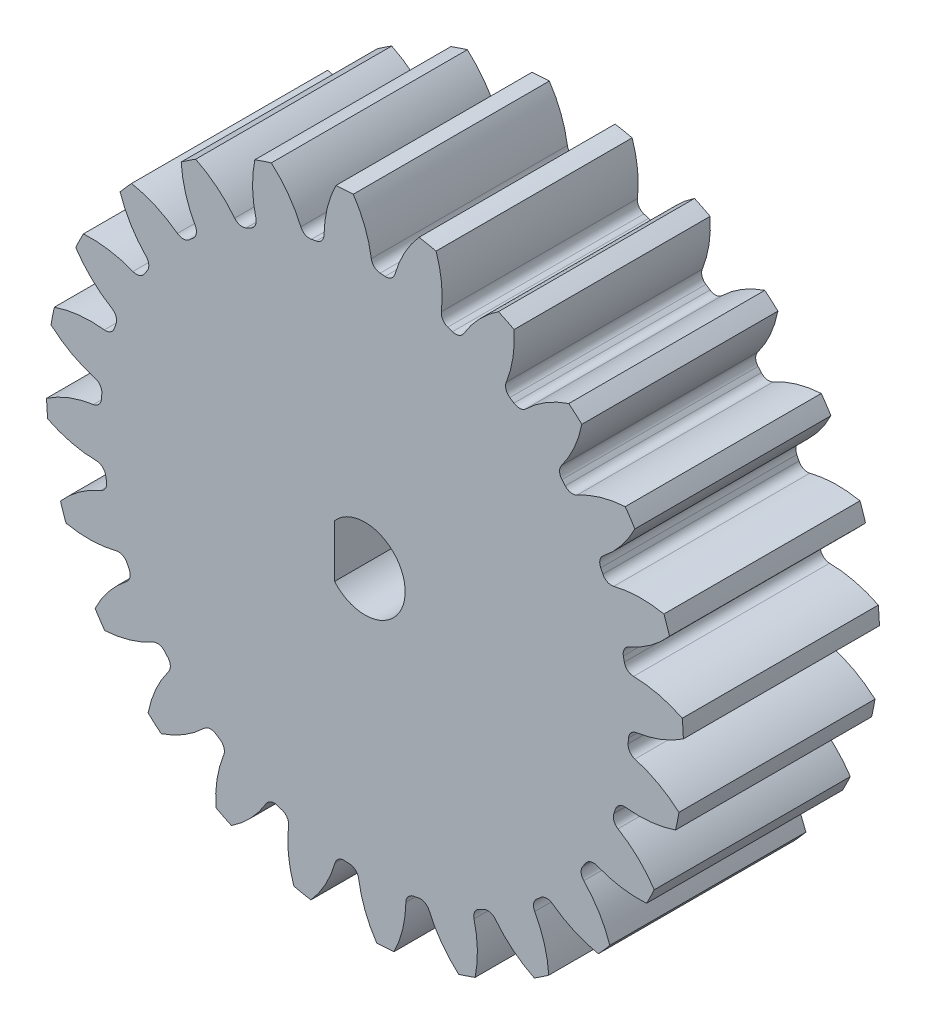
SolidWorks part; units mm, degrees
ref_plane "Front" through (0, 0, 0) normal (0, 0, 1) x (1, 0, 0)
ref_plane "Top" through (0, 0, 0) normal (0, 1, 0) x (1, 0, 0)
ref_plane "Right" through (0, 0, 0) normal (1, 0, 0) x (0, 0, -1)
sketch "Sketch3" plane through (0, 0, 0) normal (0, 0, 1) x (1, 0, 0)
  circle A0 centre (0, 0) radius 20.6375
  dimension "od" = 41.275
extrude "gearBody" add sketch "Sketch3" along normal blind 12.7
sketch "Sketch2" plane through (0, 0, 0) normal (0, 0, 1) x (1, 0, 0)
  line L0 (0, 0) -> (16.5385, 6.8505) construction
  line L1 (22.0347, -5.709) -> (0, 0) construction
  line L2 (0, 0) -> (36.3143, 0) construction
  line L3 (19.05, -0.043) -> (18.8852, -2.5004) construction
  line L5 (18.9676, -1.2717) -> (0, 0) construction
  line L7 (0, 0) -> (17.9011, 0) construction
  arc A0 (17.8975, -0.3593) -> (17.7853, -2.0332) centre (0, 0) ccw construction
  arc A1 (20.6236, 0.7563) -> (20.3381, -3.5027) centre (0, 0) ccw construction
  arc A2 (19.05, -0.043) -> (18.8852, -2.5004) centre (0, 0) ccw construction
  arc A3 (17.0444, -1.304) -> (17.0659, -0.983) centre (0, 0) ccw
  arc A4 (22.0347, -5.709) -> (17.4884, -1.9416) centre (15.476, -8.9969) ccw
  arc A5 (22.0347, -5.709) -> (22.5996, 2.7164) centre (0, 0) ccw
  arc A6 (22.5996, 2.7164) -> (17.5911, -0.4103) centre (16.5385, 6.8505) cw
  arc A7 (17.0659, -0.983) -> (17.5911, -0.4103) centre (17.6793, -1.0183) cw
  arc A8 (17.4884, -1.9416) -> (17.0444, -1.304) centre (17.657, -1.3509) cw
  point P6 (22.5996, 2.7164)
  point P22 (22.0347, -5.709)
  dimension "baseDia" = 35.8023
  dimension "od" = 41.275
  dimension "pd" = 38.1
  dimension "rd" = 34.1884
  dimension "rFillet" = 0.6144
  dimension "pointX" = 22.5996
  dimension "pointY" = 2.7164
  dimension "CTT" = 2.4574
  dimension "flankCenterAngle" = 22.5
extrude "toothCut" cut sketch "Sketch2" along normal through all
pattern_circular "CirPattern1" count 24 over 360 about axis through (0, 0, 12.7) along (0, 0, -1) of "toothCut"
sketch "hub1Dia" plane through (0, 0, 0) normal (0, 0, -1) x (-1, 0, 0)
  circle A0 centre (0, 0) radius 12.7
  dimension "hub1Dia" = 25.4
sketch "hub2Dia" plane through (0, 0, 12.7) normal (0, 0, 1) x (1, 0, 0)
  circle A0 centre (0, 0) radius 12.7
  dimension "hub2dia" = 25.4
sketch "boreDia" plane through (0, 0, 0) normal (0, 0, 1) x (1, 0, 0)
  circle A0 centre (0, 0) radius 6.35
  dimension "boreDia" = 12.7
sketch "Sketch4" plane through (0, 0, 0) normal (0, 0, -1) x (-1, 0, 0)
  line L0 (1.9685, -1.7039) -> (1.9685, 1.7039)
  line L1 (-2.6035, 4.8001) -> (-2.6035, -4.732) construction
  arc A0 (1.9685, 1.7039) -> (1.9685, -1.7039) centre (0, 0) ccw
  dimension "D1" = 5.207
  dimension "D2" = 4.572
extrude "Cut-Extrude1" cut sketch "Sketch4" against normal through all
equation "\"tightTol\" = 0.005in"
equation "\"normTol\"= 0.01in"
equation "\"looseTol\"= 0.02in"
equation "\"D1@Sketch4\"=\"tightTol\"+0.2in"
equation "\"D2@Sketch4\"=\"tightTol\"+0.175"
